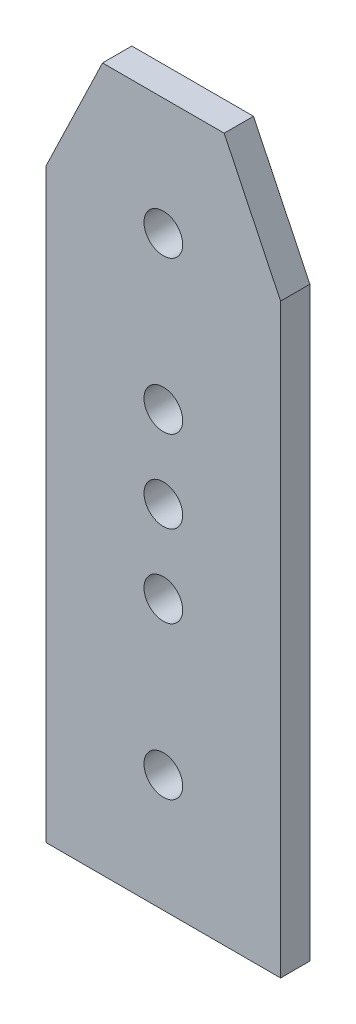
SolidWorks part; units mm, degrees
ref_plane "Front Plane" through (0, 0, 0) normal (0, 0, 1) x (1, 0, 0)
ref_plane "Top Plane" through (0, 0, 0) normal (0, 1, 0) x (1, 0, 0)
ref_plane "Right Plane" through (0, 0, 0) normal (1, 0, 0) x (0, 0, -1)
sketch "Sketch1" plane through (0, 0, 0) normal (0, 0, 1) x (1, 0, 0)
  line L0 (12.7, 25.4) -> (6.5887, 38.1)
  line L7 (-6.5887, 38.1) -> (-12.7, 25.4)
  line L15 (12.7, 25.4) -> (12.7, -38.1)
  line L16 (12.7, -38.1) -> (-12.7, -38.1)
  line L17 (-12.7, 25.4) -> (-12.7, -38.1)
  line L18 (12.7, 38.1) -> (-12.7, -38.1) construction
  line L19 (12.7, -38.1) -> (-12.7, 38.1) construction
  line L20 (-6.5887, 38.1) -> (6.5887, 38.1)
  line L21 (0, 38.1) -> (0, 0) construction
  point P0 (0, 0)
  point P5 (0, 0)
  point P8 (0, 38.1)
  point P9 (0, 0)
  point P10 (-12.7, 25.4)
  dimension "D2" = 76.2
  dimension "D3" = 12.7
  dimension "D1" = 13.1774
  dimension "D4" = 25.4
extrude "Boss-Extrude1" add sketch "Sketch1" along normal mid plane 3.175
sketch "Sketch2" plane through (0, 0, 1.5875) normal (0, 0, 1) x (1, 0, 0)
  line L0 (-12.7, -38.1) -> (12.7, -38.1) construction
  line L2 (0, 25.4) -> (0, 0) construction
  line L3 (0, 0) -> (0, -25.4) construction
  line L4 (0, -25.4) -> (0, -38.1) construction
  line L7 (6.5887, 38.1) -> (-6.5887, 38.1) construction
  circle A0 centre (0, -25.4) radius 2.0955
  circle A1 centre (0, 0) radius 2.0955
  circle A2 centre (0, 25.4) radius 2.0955
  circle A3 centre (0, -8.89) radius 2.0955
  circle A4 centre (0, 8.89) radius 2.0955
  dimension "D2" = 4.191
  dimension "D1" = 29.21
  dimension "D3" = 12.7
  dimension "D4" = 25.4
  dimension "D5" = 29.21
extrude "Cut-Extrude1" cut sketch "Sketch2" against normal through all both and the other way through all
ref_axis "Axis1" through (0, -25.4, -1.5875) along (0, 0, 1)
